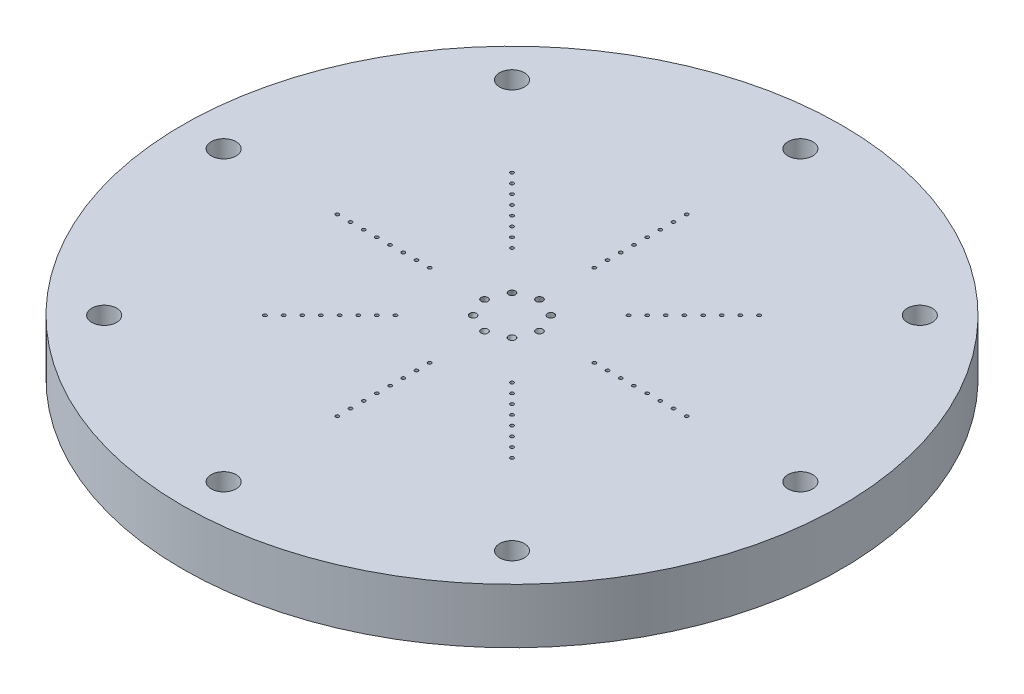
SolidWorks part; units mm, degrees
ref_plane "Front Plane" through (0, 0, 0) normal (0, 0, 1) x (1, 0, 0)
ref_plane "Top Plane" through (0, 0, 0) normal (0, 1, 0) x (1, 0, 0)
ref_plane "Right Plane" through (0, 0, 0) normal (1, 0, 0) x (0, 0, -1)
sketch "Sketch1" plane through (0, 0, 0) normal (0, 1, 0) x (1, 0, 0)
  circle A0 centre (0, 0) radius 38.1
  dimension "D1" = 76.2
extrude "Boss-Extrude1" add sketch "Sketch1" along normal blind 6.35
sketch "Sketch2" plane through (0, 0, 0) normal (0, -1, 0) x (1, 0, 0)
  circle A0 centre (0, 0) radius 33.3375
  circle A1 centre (0, 33.3375) radius 0.762
  dimension "D1" = 66.675
hole_wizard "CBORE for #4 Button Head Cap Screw1" positions "Sketch5" profile "Sketch4" counterbore size "#4" standard "ANSI Inch" end condition through all
sketch "Sketch5" plane through (0, 0, 0) normal (0, -1, 0) x (-1, 0, 0)
  point P0 (0, -33.3375)
sketch "Sketch4" plane through (0, 0, 33.3375) normal (1, 0, 0) x (0, 0, -1)
  line L0 (0, 0) -> (0, 6.35)
  line L1 (0, 6.35) -> (1.4351, 6.35)
  line L3 (1.4351, 6.35) -> (1.4351, 1.905)
  line L4 (1.4351, 1.905) -> (2.413, 1.905)
  line L5 (2.413, 1.905) -> (2.413, 0)
  line L7 (2.413, 0) -> (0, 0)
  line L11 (0, -6.35) -> (0, 107.95) construction
  dimension "Thru Hole Dia." = 2.8702
  dimension "Thru Hole Depth" = 6.35
  dimension "C'Bore Dia." = 4.826
  dimension "C'Bore Depth" = 1.905
pattern_circular "CirPattern1" count 8 over 360 about axis through (0, 0, 0) along (0, 1, 0) of "CBORE for #4 Button Head Cap Screw1"
sketch "Sketch6" plane through (0, 6.35, 0) normal (0, 1, 0) x (1, 0, 0)
  line L0 (0, 9.525) -> (0, 11.1125) construction
  line L1 (0, 9.525) -> (0, 11.049) construction
  circle A0 centre (0, 9.525) radius 0.1984
  circle A19 centre (0, 11.049) radius 0.1984
  circle A20 centre (0, 12.573) radius 0.1984
  circle A21 centre (0, 14.097) radius 0.1984
  circle A22 centre (0, 15.621) radius 0.1984
  circle A23 centre (0, 17.145) radius 0.1984
  circle A24 centre (0, 18.669) radius 0.1984
  circle A25 centre (0, 20.193) radius 0.1984
  circle A26 centre (6.7352, 6.7352) radius 0.1984
  circle A27 centre (7.8128, 7.8128) radius 0.1984
  circle A28 centre (8.8905, 8.8905) radius 0.1984
  circle A29 centre (9.9681, 9.9681) radius 0.1984
  circle A30 centre (11.0457, 11.0457) radius 0.1984
  circle A31 centre (12.1233, 12.1233) radius 0.1984
  circle A32 centre (13.201, 13.201) radius 0.1984
  circle A33 centre (14.2786, 14.2786) radius 0.1984
  circle A34 centre (9.525, 0) radius 0.1984
  circle A35 centre (11.049, 0) radius 0.1984
  circle A36 centre (12.573, 0) radius 0.1984
  circle A37 centre (14.097, 0) radius 0.1984
  circle A38 centre (15.621, 0) radius 0.1984
  circle A39 centre (17.145, 0) radius 0.1984
  circle A40 centre (18.669, 0) radius 0.1984
  circle A41 centre (20.193, 0) radius 0.1984
  circle A42 centre (6.7352, -6.7352) radius 0.1984
  circle A43 centre (7.8128, -7.8128) radius 0.1984
  circle A44 centre (8.8905, -8.8905) radius 0.1984
  circle A45 centre (9.9681, -9.9681) radius 0.1984
  circle A46 centre (11.0457, -11.0457) radius 0.1984
  circle A47 centre (12.1233, -12.1233) radius 0.1984
  circle A48 centre (13.201, -13.201) radius 0.1984
  circle A49 centre (14.2786, -14.2786) radius 0.1984
  circle A50 centre (0, -9.525) radius 0.1984
  circle A51 centre (0, -11.049) radius 0.1984
  circle A52 centre (0, -12.573) radius 0.1984
  circle A53 centre (0, -14.097) radius 0.1984
  circle A54 centre (0, -15.621) radius 0.1984
  circle A55 centre (0, -17.145) radius 0.1984
  circle A56 centre (0, -18.669) radius 0.1984
  circle A57 centre (0, -20.193) radius 0.1984
  circle A58 centre (-6.7352, -6.7352) radius 0.1984
  circle A59 centre (-7.8128, -7.8128) radius 0.1984
  circle A60 centre (-8.8905, -8.8905) radius 0.1984
  circle A61 centre (-9.9681, -9.9681) radius 0.1984
  circle A62 centre (-11.0457, -11.0457) radius 0.1984
  circle A63 centre (-12.1233, -12.1233) radius 0.1984
  circle A64 centre (-13.201, -13.201) radius 0.1984
  circle A65 centre (-14.2786, -14.2786) radius 0.1984
  circle A66 centre (-9.525, 0) radius 0.1984
  circle A67 centre (-11.049, 0) radius 0.1984
  circle A68 centre (-12.573, 0) radius 0.1984
  circle A69 centre (-14.097, 0) radius 0.1984
  circle A70 centre (-15.621, 0) radius 0.1984
  circle A71 centre (-17.145, 0) radius 0.1984
  circle A72 centre (-18.669, 0) radius 0.1984
  circle A73 centre (-20.193, 0) radius 0.1984
  circle A74 centre (-6.7352, 6.7352) radius 0.1984
  circle A75 centre (-7.8128, 7.8128) radius 0.1984
  circle A76 centre (-8.8905, 8.8905) radius 0.1984
  circle A77 centre (-9.9681, 9.9681) radius 0.1984
  circle A78 centre (-11.0457, 11.0457) radius 0.1984
  circle A79 centre (-12.1233, 12.1233) radius 0.1984
  circle A80 centre (-13.201, 13.201) radius 0.1984
  circle A81 centre (-14.2786, 14.2786) radius 0.1984
  point P135 (0, 0)
  dimension "D1" = 0.3969
  dimension "D2" = 1.5875
  dimension "D3" = 1.524
  dimension "D4" = 8
extrude "Cut-Extrude1" cut sketch "Sketch6" against normal through all
sketch "Sketch7" plane through (0, 6.35, 0) normal (0, 1, 0) x (1, 0, 0)
  circle A0 centre (0, 3.175) radius 0.3969
  dimension "D1" = 3.175
  dimension "D2" = 0.7937
sketch "Sketch8" plane through (0, 0, 0) normal (0, -1, 0) x (1, 0, 0)
  circle A0 centre (0, -4.7625) radius 0.3969
  circle A1 centre (0, -3.175) radius 0.3969 construction
  dimension "D1" = 0.7937
  dimension "D2" = 1.5875
sketch3d "3DSketch3"
  line L0 (0, 6.35, -3.175) -> (0, 0, -4.7625)
  point P2 (0, 0, -4.7625)
sweep "Cut-Sweep1" cut profiles "Sketch7" path "3DSketch3"
pattern_circular "CirPattern2" count 8 over 360 about axis through (0, 6.35, 0) along (0, 1, 0) of "Cut-Sweep1"
